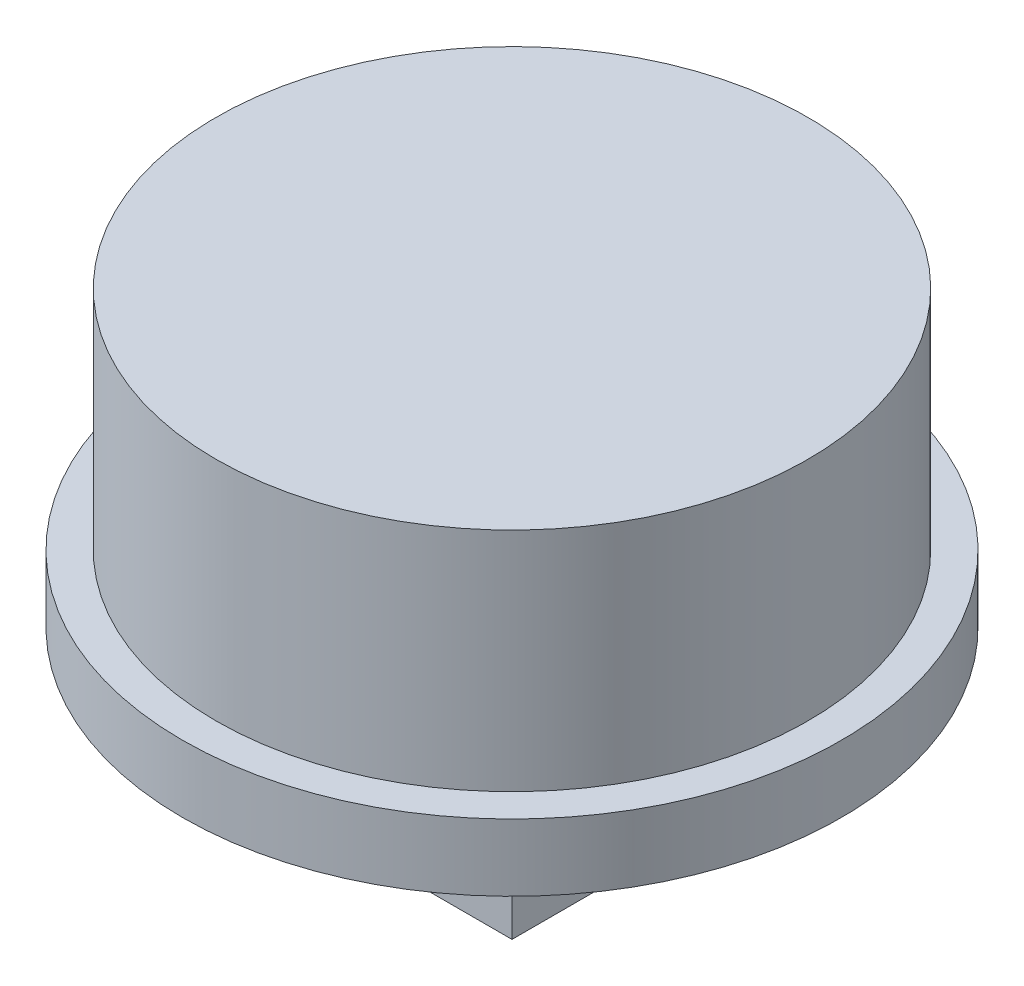
SolidWorks part; units mm, degrees
ref_plane "Front Plane" through (0, 0, 0) normal (0, 0, 1) x (1, 0, 0)
ref_plane "Top Plane" through (0, 0, 0) normal (0, 1, 0) x (1, 0, 0)
ref_plane "Right Plane" through (0, 0, 0) normal (1, 0, 0) x (0, 0, -1)
sketch "Sketch1" plane through (0, 0, 0) normal (0, 1, 0) x (1, 0, 0)
  circle A0 centre (0, 0) radius 6.4
  circle A1 centre (0, 0) radius 4.9
  circle A2 centre (0, 0) radius 5.75
  dimension "D1" = 12.8
  dimension "D2" = 9.8
  dimension "D3" = 11.5
extrude "Boss-Extrude1" add sketch "Sketch1" along normal blind 1.3 contours A0
extrude "Boss-Extrude2" add sketch "Sketch1<3>" along normal blind 5.7 contours A2
sketch "Sketch1<3>" plane through (0, 0, 0) normal (0, 1, 0) x (1, 0, 0) same geometry as "Sketch1"
sketch "Sketch2" plane through (0, 0, 0) normal (0, 1, 0) x (1, 0, 0)
  line L1 (2.75, 2.75) -> (-2.75, 2.75)
  line L2 (2.75, 2.75) -> (2.75, -2.75)
  line L3 (2.75, -2.75) -> (-2.75, -2.75)
  line L4 (-2.75, 2.75) -> (-2.75, -2.75)
  line L5 (2.75, 2.75) -> (-2.75, -2.75) construction
  line L6 (2.75, -2.75) -> (-2.75, 2.75) construction
  line L7 (1.9, 1.9) -> (-1.9, 1.9)
  line L8 (1.9, 1.9) -> (1.9, -1.9)
  line L9 (1.9, -1.9) -> (-1.9, -1.9)
  line L10 (-1.9, 1.9) -> (-1.9, -1.9)
  line L11 (1.9, 1.9) -> (-1.9, -1.9) construction
  line L12 (1.9, -1.9) -> (-1.9, 1.9) construction
  point P0 (0, 0)
  point P6 (0, 0)
  dimension "D1" = 5.5
  dimension "D2" = 3.8
extrude "Boss-Extrude3" add sketch "Sketch2" against normal blind 2.5
